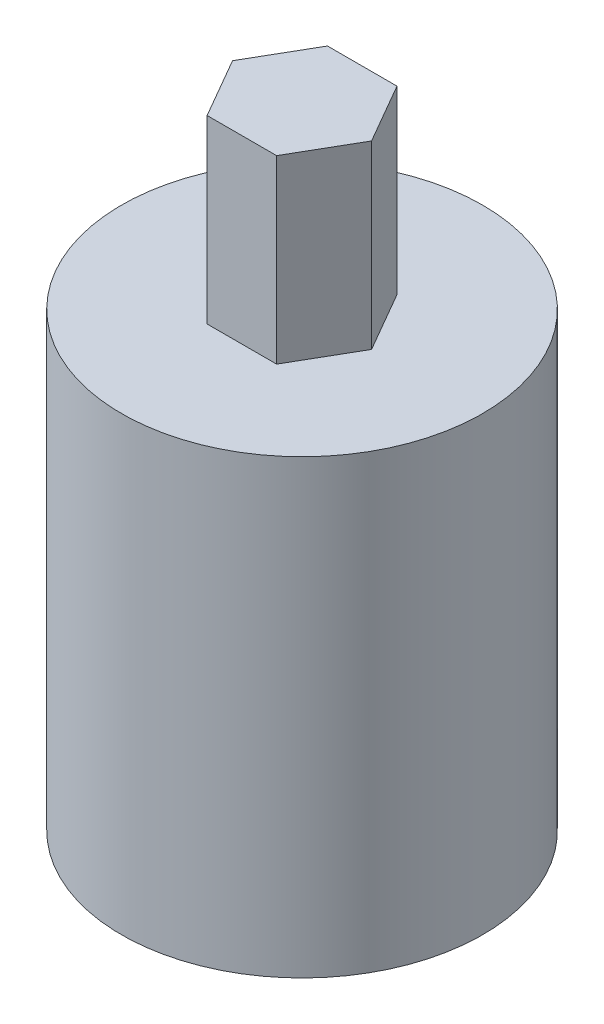
SolidWorks part; units mm, degrees
ref_plane "前视基准面" through (0, 0, 0) normal (0, 0, 1) x (1, 0, 0)
ref_plane "上视基准面" through (0, 0, 0) normal (0, 1, 0) x (1, 0, 0)
ref_plane "右视基准面" through (0, 0, 0) normal (1, 0, 0) x (0, 0, -1)
other "Configuration Table"
sketch "草图1" plane through (0, 0, 0) normal (0, 1, 0) x (1, 0, 0)
  line L1 (0.5774, 1) -> (-0.5774, 1)
  line L2 (-0.5774, 1) -> (-1.1547, 0)
  line L3 (-1.1547, 0) -> (-0.5774, -1)
  line L4 (-0.5774, -1) -> (0.5774, -1)
  line L5 (0.5774, -1) -> (1.1547, 0)
  line L6 (1.1547, 0) -> (0.5774, 1)
  circle A1 centre (0, 0) radius 1 construction
  point P0 (0, 0)
  dimension "D1" = 2
extrude "凸台-拉伸1" add sketch "草图1" along normal blind 3 contours L2 L3 L4 L5 L6 L1
sketch "草图2" plane through (0, 0, 0) normal (0, -1, 0) x (1, 0, 0)
  line L1 (-1.13, -2.23) -> (1.13, -2.23)
  line L2 (-1.13, -2.23) -> (-1.13, 2.23)
  line L3 (-1.13, 2.23) -> (1.13, 2.23)
  line L4 (1.13, -2.23) -> (1.13, 2.23)
  line L5 (-1.13, -2.23) -> (1.13, 2.23) construction
  line L6 (-1.13, 2.23) -> (1.13, -2.23) construction
  line L7 (-2.23, -1.13) -> (2.23, -1.13)
  line L8 (-2.23, -1.13) -> (-2.23, 1.13)
  line L9 (-2.23, 1.13) -> (2.23, 1.13)
  line L10 (2.23, -1.13) -> (2.23, 1.13)
  line L11 (-2.23, -1.13) -> (2.23, 1.13) construction
  line L12 (-2.23, 1.13) -> (2.23, -1.13) construction
  circle A0 centre (0, 0) radius 3
  circle A1 centre (0, 0) radius 2.5
  point P11 (0, 0)
  dimension "D1" = 5
  dimension "D2" = 6
  dimension "D3" = 1.1
extrude "凸台-拉伸2" add sketch "草图2" along normal blind 7.5 separate body contours A0
extrude "切除-拉伸1" cut sketch "草图2<3>" against normal offset from surface (6.5 mm away) 1 from surface contours L3 A1 | L8 A1 | L1 A1 | L10 A1 | L3 L4 L1 L2 | L9 L10 L7 L8 region at (0, 0, -2.3385) region at (-2.3385, 0, 0) region at (2.3385, 0, 0) region at (0, 0, 2.3385) up to face at (0, 0, -3) starting at face at (0, -7.5, -3)
sketch "草图2<3>" plane through (0, 0, 0) normal (0, -1, 0) x (1, 0, 0) same geometry as "草图2"
